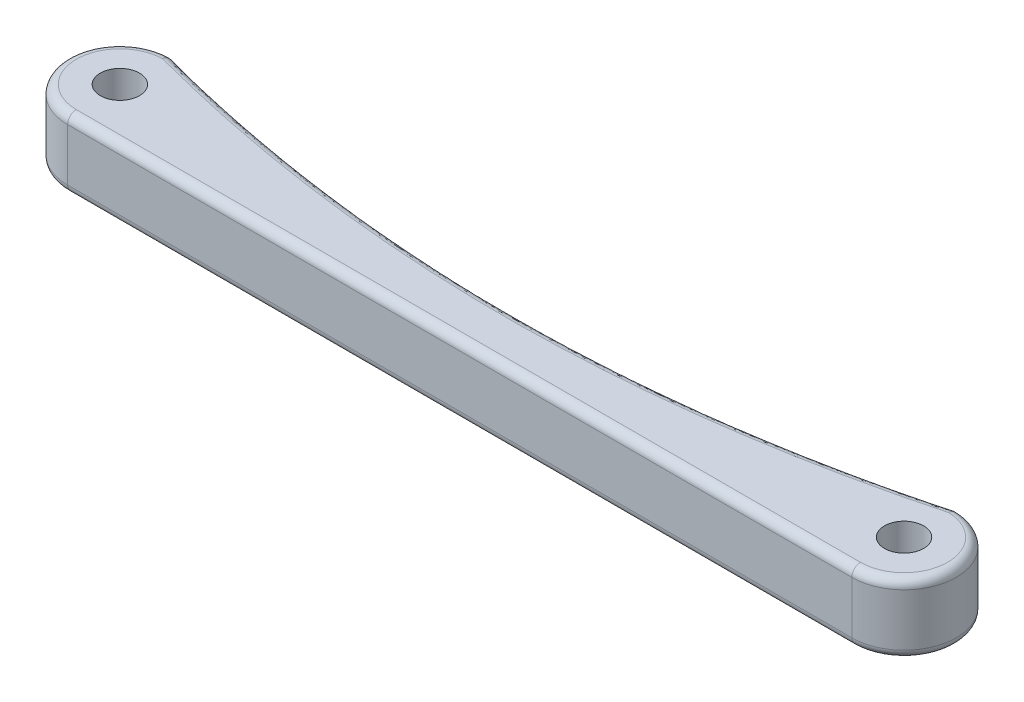
SolidWorks part; units mm, degrees
ref_plane "Front Plane" through (0, 0, 0) normal (0, 0, 1) x (1, 0, 0)
ref_plane "Top Plane" through (0, 0, 0) normal (0, 1, 0) x (1, 0, 0)
ref_plane "Right Plane" through (0, 0, 0) normal (1, 0, 0) x (0, 0, -1)
sketch "Sketch2" plane through (0, 0, 0) normal (0, 1, 0) x (1, 0, 0)
  line L0 (0, 0) -> (45, 0) construction
  line L1 (0, 3) -> (45, 3)
  line L2 (0, -3) -> (45, -3)
  arc A0 (0, 3) -> (0, -3) centre (0, 0) ccw
  arc A1 (45, -3) -> (45, 3) centre (45, 0) ccw
  circle A2 centre (0, 0) radius 1.125
  circle A3 centre (45, 0) radius 1.125
  point P3 (22.5, 0)
  dimension "D2" = 2.25
  dimension "D1" = 45
  dimension "D3" = 6
extrude "Boss-Extrude1" add sketch "Sketch2" along normal blind 4
sketch "Sketch3" plane through (0, 4, 0) normal (0, 1, 0) x (1, 0, 0)
  line L0 (45, 3) -> (0, 3) construction
  line L1 (0, 3) -> (45, 3)
  spline S0 degree 2 poles (0, 3) (22.5, -3) (45, 3) knots 0 0 0 1 1 1
  point P8 (22.5, 3)
extrude "Cut-Extrude1" cut sketch "Sketch3" against normal through all both and the other way through all
fillet "Fillet2" radius 0.5 10 edges at (48, 0, 0) (22.5, 0, 3) (48, 4, 0) (22.5, 4, 3) (-3, 0, 0) (-3, 4, 0) (45, 2, -3) (0, 2, -3)
